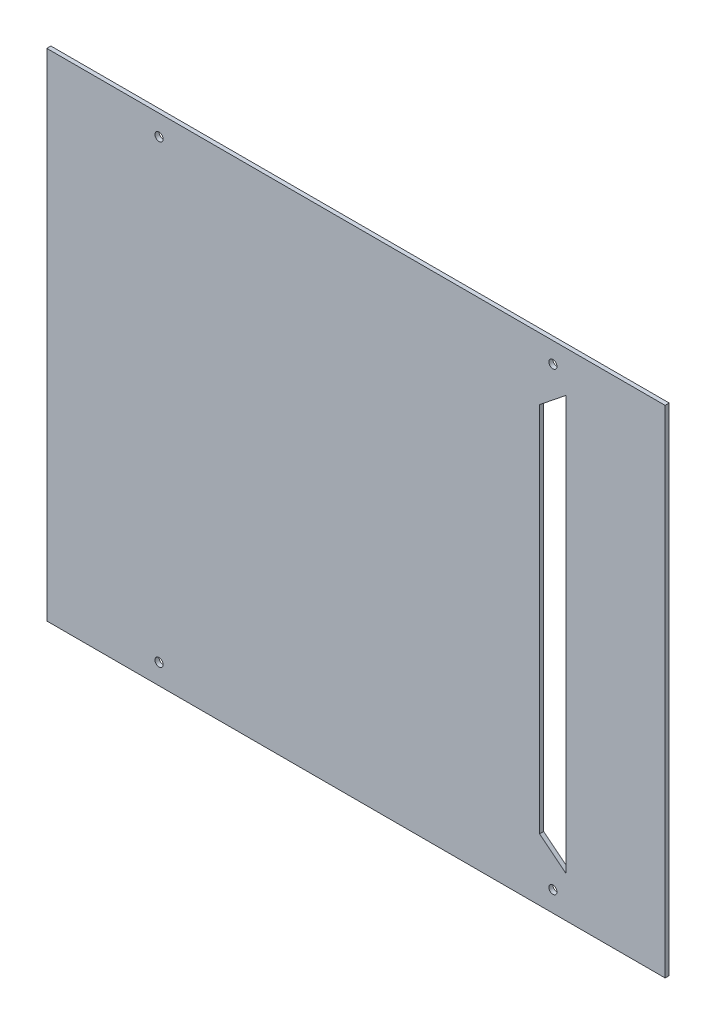
SolidWorks part; units mm, degrees
ref_plane "Front Plane" through (0, 0, 0) normal (0, 0, 1) x (1, 0, 0)
ref_plane "Top Plane" through (0, 0, 0) normal (0, 1, 0) x (1, 0, 0)
ref_plane "Right Plane" through (0, 0, 0) normal (1, 0, 0) x (0, 0, -1)
sketch "Sketch1" plane through (0, 0, 0) normal (0, 0, 1) x (1, 0, 0)
  line L0 (0, 0) -> (-206.9982, 0) construction
  line L1 (151.5, -121.5) -> (-151.5, -121.5)
  line L2 (151.5, -121.5) -> (151.5, 121.5)
  line L3 (151.5, 121.5) -> (-151.5, 121.5)
  line L4 (-151.5, -121.5) -> (-151.5, 121.5)
  line L5 (151.5, -121.5) -> (-151.5, 121.5) construction
  line L6 (151.5, 121.5) -> (-151.5, -121.5) construction
  line L7 (139.0309, -111.5) -> (-139.0309, -111.5) construction
  line L8 (139.0309, -111.5) -> (139.0309, 111.5) construction
  line L9 (139.0309, 111.5) -> (-139.0309, 111.5) construction
  line L10 (-139.0309, -111.5) -> (-139.0309, 111.5) construction
  line L11 (139.0309, -111.5) -> (-139.0309, 111.5) construction
  line L12 (139.0309, 111.5) -> (-139.0309, -111.5) construction
  line L13 (103, 101.5) -> (103, -101.5)
  line L14 (90, 91.0743) -> (90, -91.0743)
  line L15 (103, 101.5) -> (90, 91.0743)
  line L16 (103, -101.5) -> (90, -91.0743)
  circle A0 centre (-96.5, 111.5) radius 2
  circle A1 centre (96.5, 111.5) radius 2
  circle A2 centre (96.5, -111.5) radius 2
  circle A3 centre (-96.5, -111.5) radius 2
  point P0 (0, 0)
  point P5 (0, 0)
  dimension "D4" = 4
  dimension "D5" = 4
  dimension "D1" = 303
  dimension "D2" = 243
  dimension "D3" = 10
  dimension "D6" = 55
  dimension "D7" = 55
  dimension "D8" = 48.5
  dimension "D9" = 13
  dimension "D10" = 10
  dimension "D11" = 10
extrude "Boss-Extrude1" add sketch "Sketch1" along normal blind 2
